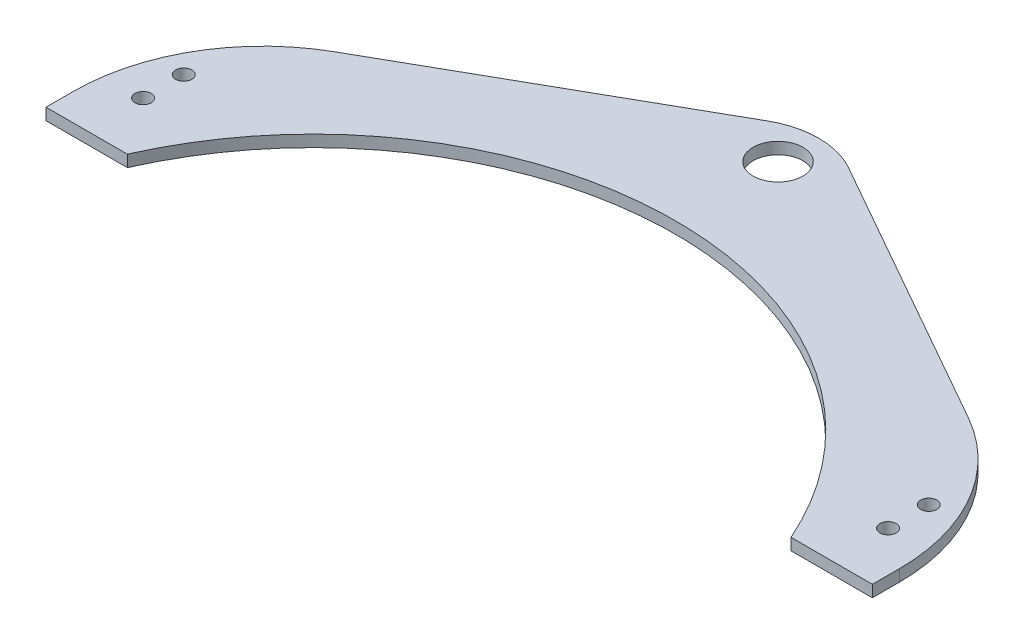
SolidWorks part; units mm, degrees
ref_plane "Front Plane" through (0, 0, 0) normal (0, 0, 1) x (1, 0, 0)
ref_plane "Top Plane" through (0, 0, 0) normal (0, 1, 0) x (1, 0, 0)
ref_plane "Right Plane" through (0, 0, 0) normal (1, 0, 0) x (0, 0, -1)
sketch "Sketch1" plane through (0, 0, 0) normal (0, 1, 0) x (1, 0, 0)
  line L0 (0, 0) -> (122.4, 0)
  line L1 (61.2, 0) -> (61.2, 39.9)
  line L2 (122.4, 0) -> (137.4, 0)
  line L3 (0, 0) -> (-15, 0)
  line L4 (137.4, 0) -> (137.4, 16.6577)
  line L5 (-15, 0) -> (-15, 16.6577)
  line L6 (61.2, 0) -> (61.2, 58.8)
  line L7 (61.2, 58.8) -> (61.2, 66.3)
  line L8 (61.2, 66.3) -> (61.2465, 66.3)
  line L9 (61.2, 66.3) -> (61.1535, 66.3)
  line L10 (68.6399, 64.3514) -> (129.7934, 29.709)
  line L11 (53.7601, 64.3514) -> (-7.3934, 29.709)
  line L12 (129.9, 0) -> (129.9, 10.4)
  line L13 (129.9, 10.4) -> (129.9, 17.9)
  line L14 (-7.5, 0) -> (-7.5, 10.4)
  line L15 (119.6512, 35.4544) -> (68.6399, 64.3514)
  line L16 (137.4, 5.0012) -> (137.4, 0)
  line L17 (53.7601, 64.3514) -> (2.7488, 35.4544)
  line L18 (-15, 5.0012) -> (-15, 0)
  line L19 (-7.5, 10.4) -> (-7.5, 17.9)
  arc A0 (0, 0) -> (122.4, 0) centre (61.2, -26.9726) cw
  circle A1 centre (61.2, 58.8) radius 4.6
  arc A2 (61.2465, 66.3) -> (68.6399, 64.3514) centre (61.2465, 51.3) cw
  arc A3 (61.1535, 66.3) -> (53.7601, 64.3514) centre (61.1535, 51.3) ccw
  arc A4 (-15, 16.6577) -> (-7.3934, 29.709) centre (0, 16.6577) cw
  arc A5 (137.4, 16.6577) -> (129.7934, 29.709) centre (122.4, 16.6577) ccw
  circle A6 centre (129.9, 17.9) radius 1.5
  circle A7 centre (129.9, 10.4) radius 1.5
  arc A10 (119.6512, 35.4544) -> (137.4, 5.0012) centre (102.4, 5.0012) cw
  arc A11 (2.7488, 35.4544) -> (-15, 5.0012) centre (20, 5.0012) ccw
  circle A13 centre (-7.5, 17.9) radius 1.5
  circle A14 centre (-7.5, 10.4) radius 1.5
  point P17 (65.2, 66.3)
  point P20 (57.2, 66.3)
  point P23 (-15, 25.4)
  point P26 (137.4, 25.4)
  point P41 (137.4, 25.4)
  point P44 (-15, 25.4)
  dimension "D8" = 7.5
  dimension "D11" = 15
  dimension "D12" = 15
  dimension "D15" = 10.4
  dimension "D16" = 35
  dimension "D17" = 7.5
  dimension "D1" = 122.4
  dimension "D2" = 39.9
  dimension "D3" = 15
  dimension "D4" = 15
  dimension "D5" = 25.4
  dimension "D6" = 25.4
  dimension "D7" = 58.8
  dimension "D9" = 4
  dimension "D10" = 4
  dimension "D13" = 10.4
  dimension "D14" = 7.5
extrude "Boss-Extrude2" add sketch "Sketch1" along normal blind 3.175 contours L11 A11 L5 L3 A13 A0 L6 A1 L7 L9 A3 | A10 L10 A2 L8 L7 A1 L6 A0 L2 A7 A6 L4 region at (21.8428, 0, -33.4988) region at (100.5572, 0, -33.4988)
sketch "Sketch2" plane through (0, 3.175, 0) normal (0, 1, 0) x (1, 0, 0)
  line L1 (-67.6712, -28.5428) -> (168.2941, -28.5428)
  line L2 (-67.6712, -28.5428) -> (-67.6712, 90.1788)
  line L3 (-67.6712, 90.1788) -> (168.2941, 90.1788)
  line L4 (168.2941, -28.5428) -> (168.2941, 90.1788)
extrude "Cut-Extrude1" cut sketch "Sketch2" against normal blind 1.016
